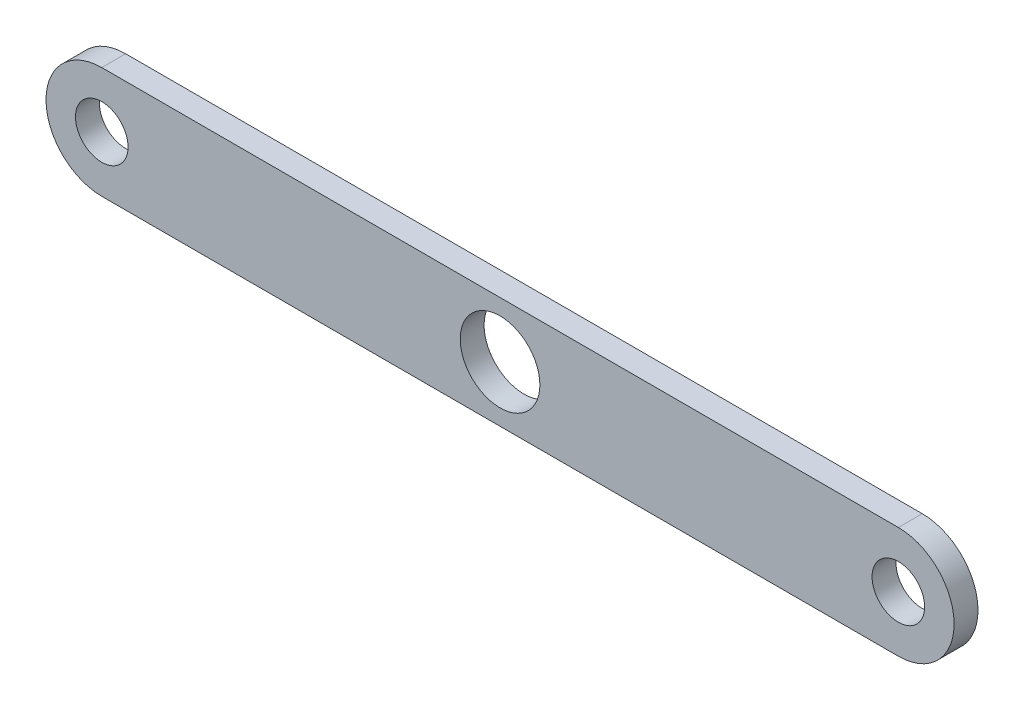
SolidWorks part; units mm, degrees
ref_plane "Front Plane" through (0, 0, 0) normal (0, 0, 1) x (1, 0, 0)
ref_plane "Top Plane" through (0, 0, 0) normal (0, 1, 0) x (1, 0, 0)
ref_plane "Right Plane" through (0, 0, 0) normal (1, 0, 0) x (0, 0, -1)
sketch "Sketch1" plane through (0, 0, 0) normal (0, 0, 1) x (1, 0, 0)
  circle B0 centre (-7.4732, -0.0105) radius 2.5
  circle B1 centre (17.5268, -0.0105) radius 1.65
  circle B2 centre (-32.4732, -0.0105) radius 1.65
  line B3 (-32.4732, 3.4895) -> (17.5268, 3.4895)
  arc B4 (17.5268, -3.5105) -> (17.5268, 3.4895) centre (17.5268, -0.0105) ccw
  line B5 (-32.4732, -3.5105) -> (17.5268, -3.5105)
  arc B6 (-32.4732, 3.4895) -> (-32.4732, -3.5105) centre (-32.4732, -0.0105) ccw
  line B7 (-32.4732, -0.0105) -> (17.5268, -0.0105) construction
sketch_block_instance "Block-center_link-1"
sketch_block "Block-center_link" parameters "D1"=3.3, "D2"=3.3, "D3"=5, "D4"=50, "D5"=7
extrude "Boss-Extrude1" add sketch "Sketch1" along normal blind 1.5
